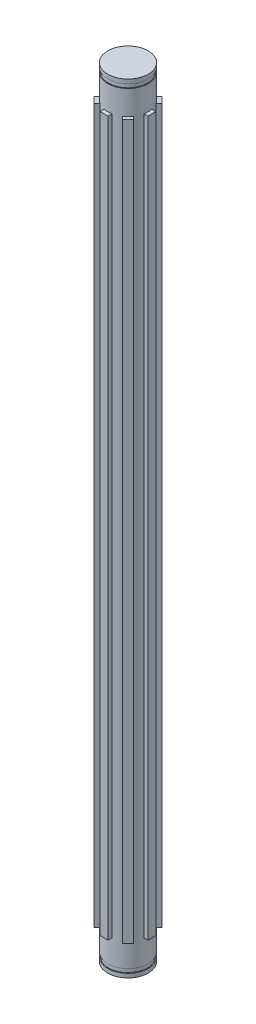
SolidWorks part; units mm, degrees
material "PE High Density"
ref_plane "Front Plane" through (0, 0, 0) normal (0, 0, 1) x (1, 0, 0)
ref_plane "Top Plane" through (0, 0, 0) normal (0, 1, 0) x (1, 0, 0)
ref_plane "Right Plane" through (0, 0, 0) normal (1, 0, 0) x (0, 0, -1)
sketch "Sketch3" plane through (0, 0, 0) normal (1, 0, 0) x (0, 0, -1)
  line L0 (0, 96) -> (5, 96)
  line L1 (0, 0) -> (5, 0)
  line L2 (0, 0) -> (0, 96)
  line L4 (5, 0) -> (5, 96)
  line L5 (5, 1) -> (4.8, 1)
  line L6 (5, 1) -> (5, 2)
  line L7 (5, 2) -> (4.8, 2)
  line L8 (4.8, 1) -> (4.8, 2)
  line L17 (2.5, 2) -> (2.5, 8) construction
  line L18 (0, 2) -> (5, 2) construction
  line L19 (0, 8) -> (5, 8) construction
  dimension "D1" = 6
  dimension "D2" = 5
  dimension "D3" = 4.8
  dimension "D4" = 1
  dimension "D5" = 1
  dimension "D6" = 88
revolve "Revolve1" add sketch "Sketch3" angle 360 about L2 region at (0, 48.0194, -2.499)
sketch "Sketch4" plane through (0, 0, 0) normal (0, -1, 0) x (1, 0, 0)
  line L0 (-1, 4.899) -> (-1, 5.899)
  line L1 (-1, 5.899) -> (1, 5.899)
  line L2 (1, 5.899) -> (1, 4.899)
  line L3 (0, 0) -> (0, 15.0182) construction
  circle A0 centre (0, 0) radius 5 construction
  arc A1 (-1, 4.899) -> (1, 4.899) centre (0, 0) cw
  circle M6 centre (0, 0) radius 5
  dimension "D1" = 2
  dimension "D2" = 1
extrude "Boss-Extrude2" add sketch "Sketch4" against normal through all from vertex contours A1 L3 L1 L0 | L3 L2 L1 M6 region at (-0.509, 0, 5.4322) region at (0.509, 0, 5.4322) starting at point (0, 8, -5)
pattern_circular "CirPattern1" count 8 over 360 about axis through (0, 0, 0) along (0, -1, 0) of "Boss-Extrude2"
mirror "Mirror1" about plane through (0, 96, 0) normal (0, -1, 0) of bodies 104 102
